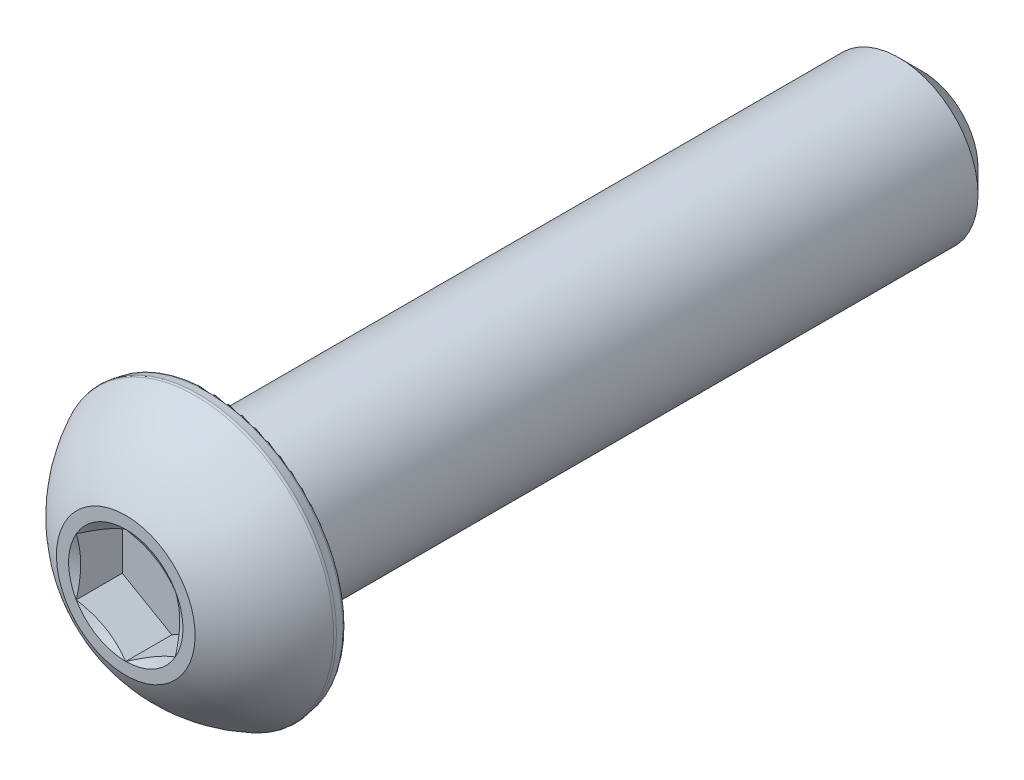
SolidWorks part; units mm, degrees
ref_plane "Front Plane" through (0, 0, 0) normal (0, 0, 1) x (1, 0, 0)
ref_plane "Top Plane" through (0, 0, 0) normal (0, 1, 0) x (1, 0, 0)
ref_plane "Right Plane" through (0, 0, 0) normal (1, 0, 0) x (0, 0, -1)
sketch "Sketch1" plane through (0, 0, 0) normal (1, 0, 0) x (0, 0, -1)
  line L0 (-15.9639, 0) -> (15.9639, 0) construction
  line L1 (-15.9639, 0) -> (-15.9639, 5.5499)
  line L2 (-15.9639, 5.5499) -> (-12.6111, 5.5499)
  line L3 (-12.6111, 5.5499) -> (-12.6111, 3.175)
  line L4 (-12.6111, 3.175) -> (15.9639, 3.175)
  line L5 (15.9639, 3.175) -> (15.9639, 0)
  point P2 (0, 0)
  point P4 (14.6939, 0)
  point P9 (14.0589, 3.175)
  point P10 (14.0589, -3.175)
  point P11 (15.9639, -3.175)
  point P15 (-14.1199, 0)
  dimension "Head Height" = 3.3528
  dimension "Head Diameter" = 11.0998
  dimension "Length" = 28.575
  dimension "Screw Size Decimal Equivalent" = 6.35
  dimension "Thread Pitch" = 1.27
  dimension "D1" = 1.905
  dimension "D2" = 1.844
sketch "Sketch2" plane through (0, 0, 0) normal (0, 0, 1) x (1, 0, 0)
  line L0 (0, 3.175) -> (0, 0) construction
  line L1 (0, 2.2914) -> (-1.9844, 1.1457)
  line L2 (-1.9844, 1.1457) -> (-1.9844, -1.1457)
  line L3 (-1.9844, -1.1457) -> (0, -2.2914)
  line L4 (0, -2.2914) -> (1.9844, -1.1457)
  line L5 (1.9844, -1.1457) -> (1.9844, 1.1457)
  line L6 (1.9844, 1.1457) -> (0, 2.2914)
  circle A0 centre (0, 0) radius 1.9844 construction
  circle A1 centre (0, 0) radius 2.7781
  point P10 (0, 2.7781)
  dimension "D1" = 5.5563
  dimension "Drive Size" = 3.9688
sketch "Sketch3" plane through (0, 0, 0) normal (1, 0, 0) x (0, 0, -1)
  line L0 (-15.9639, 0) -> (-15.9639, 2.7781)
  line L1 (-15.9639, 0) -> (-15.9639, 5.5499) construction
  line L2 (-15.9639, 5.5499) -> (-12.6111, 5.5499) construction
  line L3 (-13.114, 5.5499) -> (-12.6111, 5.4612)
  line L4 (-12.6111, 5.5499) -> (-12.6111, 3.175) construction
  line L5 (-12.6111, 5.4612) -> (-12.6111, 3.175)
  line L6 (-15.9639, 0) -> (15.9639, 0) construction
  line L7 (-15.9639, 0) -> (15.9639, 0)
  line L8 (15.9639, 0) -> (15.9639, 2.2225)
  line L9 (15.9639, 3.175) -> (15.9639, 0) construction
  line L10 (15.9639, 2.2225) -> (15.0114, 3.175)
  line L11 (-12.6111, 3.175) -> (15.9639, 3.175) construction
  line L12 (15.0114, 3.175) -> (-12.6111, 3.175)
  arc A0 (-15.9639, 2.7781) -> (-13.114, 5.5499) centre (-10.4891, 0) cw
  dimension "D1" = 0.5029
  dimension "D2" = 10
  dimension "D3" = 45
  dimension "D4" = 0.9525
revolve "Revolve1" add sketch "Sketch3" angle 360 about L7
sketch "Sketch4" plane through (0, 0, 15.9639) normal (0, 0, 1) x (1, 0, 0)
  line L0 (-1.9844, -1.1457) -> (0, -2.2914) construction
  line L1 (-1.9844, 1.1457) -> (-1.9844, -1.1457) construction
  line L2 (0, 2.2914) -> (-1.9844, 1.1457) construction
  line L3 (1.9844, 1.1457) -> (0, 2.2914) construction
  line L4 (1.9844, -1.1457) -> (1.9844, 1.1457) construction
  line L5 (0, -2.2914) -> (1.9844, -1.1457) construction
  line L6 (-1.9844, -1.1457) -> (0, -2.2914)
  line L7 (-1.9844, 1.1457) -> (-1.9844, -1.1457)
  line L8 (0, 2.2914) -> (-1.9844, 1.1457)
  line L9 (1.9844, 1.1457) -> (0, 2.2914)
  line L10 (1.9844, -1.1457) -> (1.9844, 1.1457)
  line L11 (0, -2.2914) -> (1.9844, -1.1457)
extrude "Cut-Extrude1" cut sketch "Sketch4" against normal up to vertex (1.844 mm away) up to point (0, 0, 14.1199)
sketch "Sketch5" plane through (0, 0, 15.9639) normal (0, 0, 1) x (1, 0, 0)
  circle A0 centre (0, 0) radius 2.2914
extrude "Cut-Extrude2" cut sketch "Sketch5" against normal up to vertex (1.844 mm away) draft 60 up to point (0, 0, 14.1199)
fillet "Fillet1" radius 0.1676 2 edges at (5.5499, 0, 13.114) (5.4612, 0, 12.6111)
split "Split1" [suppressed] bodies to split 106
sketch "Sketch6" [suppressed] plane through (0, 0, -15.9639) normal (0, 0, -1) x (-1, 0, 0)
  circle A0 centre (0, 0) radius 3.175 construction
  circle A1 centre (0, 0) radius 3.175
curve "Helix/Spiral1" [suppressed] pitch 1.27 height 29.845 turns 23.5
sketch "Sketch7" [suppressed] plane through (0, 0, 0) normal (1, 0, 0) x (0, 0, -1)
  line L0 (15.8845, 3.3125) -> (16.5195, 2.2126) construction
  line L1 (16.5195, 2.2126) -> (17.1545, 3.3125) construction
  line L2 (17.1545, 3.3125) -> (15.8845, 3.3125) construction
  line L3 (15.9242, 3.2437) -> (17.1148, 3.2437)
  line L4 (17.1148, 3.2437) -> (16.5989, 2.3501)
  line L5 (16.5989, 2.3501) -> (16.4402, 2.3501)
  line L6 (16.4402, 2.3501) -> (15.9242, 3.2437)
  line L7 (16.5195, 2.3501) -> (16.5195, 2.2126) construction
  line L8 (15.9639, 3.175) -> (17.0752, 3.175) construction
  line L9 (16.5195, 3.3125) -> (16.5195, 3.175) construction
  point P12 (16.5195, 3.2437)
  dimension "D1" = 1.27
  dimension "D2" = 0.1588
sweep "Cut-Sweep1" [suppressed] cut profiles "Sketch7" path "Helix/Spiral1"
sketch "Sketch8" [suppressed] plane through (0, 0, 12.6111) normal (0, 0, -1) x (-1, 0, 0)
  circle A0 centre (0, 0) radius 3.3125
extrude "Boss-Extrude1" [suppressed] add sketch "Sketch8" along normal up to vertex draft 45
equation "\"D1@Sketch1\"=\"Thread Pitch@Sketch1\"*1.5"
equation "\"D2@Sketch1\"=0.55*\"Head Height@Sketch1\""
equation "\"D1@Sketch2\"=\"Drive Size@Sketch2\"*1.4"
equation "\"D1@Sketch3\"=0.15*\"Head Height@Sketch1\""
equation "\"D4@Sketch3\"=0.75*\"Thread Pitch@Sketch1\""
equation "\"D1@Fillet1\"=.05*\"Head Height@Sketch1\""
equation "\"D4@Helix/Spiral1\"=\"Thread Pitch@Sketch1\""
equation "\"D3@Helix/Spiral1\"=\"Length@Sketch1\"+\"Thread Pitch@Sketch1\""
equation "\"D2@Sketch7\"=\"D1@Sketch7\"/8"
equation "\"D1@Sketch7\"=\"Thread Pitch@Sketch1\""
